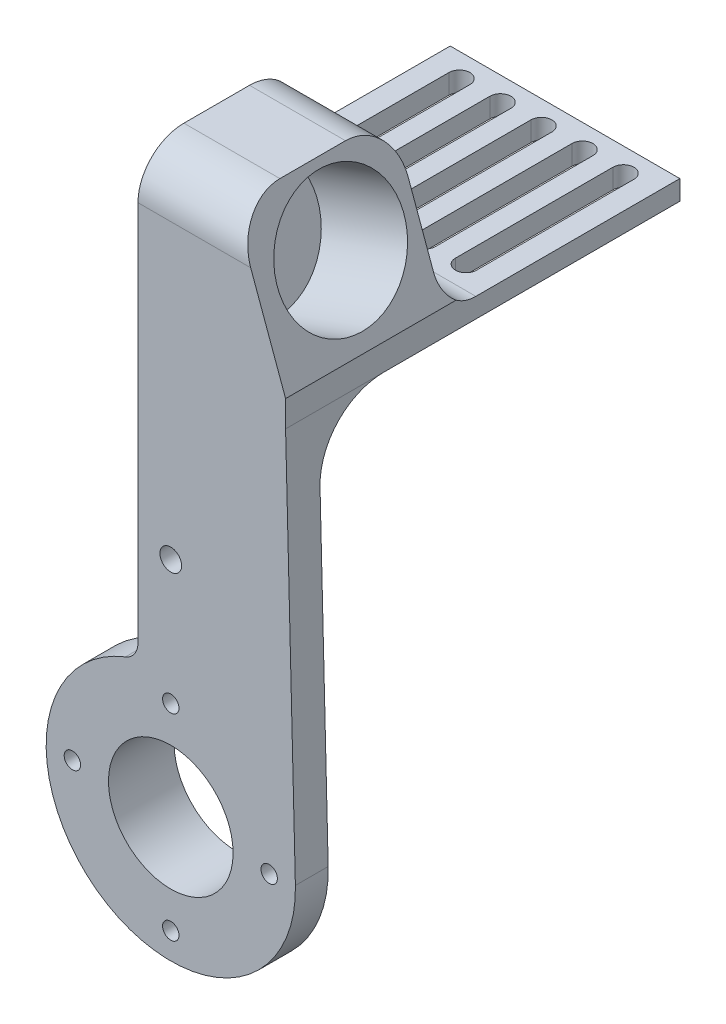
SolidWorks part; units mm, degrees
material "7075-T6 (SN)"
ref_plane "Front Plane" through (0, 0, 0) normal (0, 0, 1) x (1, 0, 0)
ref_plane "Top Plane" through (0, 0, 0) normal (0, 1, 0) x (1, 0, 0)
ref_plane "Right Plane" through (0, 0, 0) normal (1, 0, 0) x (0, 0, -1)
sketch "Sketch2" plane through (0, 0, 0) normal (0, 0, 1) x (1, 0, 0)
  line L0 (-18.994, 0.4767) -> (-17.5, 60)
  line L1 (-17.5, 60) -> (17.5, 60)
  line L2 (17.5, 60) -> (18.994, 0.4767)
  circle A0 centre (0, 0) radius 9.5
  arc A1 (-18.994, 0.4767) -> (18.994, 0.4767) centre (0, 0) ccw
  dimension "D1" = 19
  dimension "D2" = 38
  dimension "D3" = 60
  dimension "D4" = 35
extrude "Boss-Extrude1" add sketch "Sketch2" along normal blind 5
sketch "Sketch3" plane through (0, 60, 0) normal (0, 1, 0) x (1, 0, 0)
  line L1 (-17.5, -5) -> (17.5, -5)
  line L2 (-17.5, -5) -> (-17.5, 80.128)
  line L3 (-17.5, 80.128) -> (17.5, 80.128)
  line L4 (17.5, -5) -> (17.5, 80.128)
  dimension "D1" = 85.128
extrude "Boss-Extrude2" add sketch "Sketch3" along normal blind 3
sketch "Sketch4" plane through (0, 0, 0) normal (0, 0, -1) x (-1, 0, 0)
  circle A0 centre (0, 0) radius 13
  circle A2 centre (0, 0) radius 9.5
  circle A3 centre (0, 0) radius 9.5 construction
  dimension "D1" = 26
extrude "Boss-Extrude3" add sketch "Sketch4" along normal blind 5
sketch "Sketch5" plane through (0, 0, -80.128) normal (0, 0, -1) x (-1, 0, 0)
  line L0 (-17.5, 60) -> (-17.5, 51)
  line L1 (-17.5, 51) -> (17.5, 51)
  line L2 (17.5, 51) -> (17.5, 60)
  line L3 (17.5, 60) -> (-17.5, 60)
  dimension "D1" = 9
extrude "Boss-Extrude4" add sketch "Sketch5" against normal blind 3
hole_wizard "M3x0.5 Tapped Hole1" positions "Sketch8" profile "Sketch7" tap size "M3x0.5" standard "ANSI Metric"
sketch "Sketch8" plane through (0, 0, -80.128) normal (0, 0, 1) x (1, 0, 0)
  line L1 (-12, 55.5) -> (0, 55.5) construction
  line L2 (0, 55.5) -> (12, 55.5) construction
  line L5 (0, 55.5) -> (0, 63) construction
  line L6 (-17.5, 63) -> (17.5, 63) construction
  line L8 (17.5, 60) -> (-17.5, 60) construction
  point P2 (12, 55.5)
  point P4 (0, 55.5)
  point P6 (-12, 55.5)
  dimension "D1" = 12
  dimension "D2" = 4.5
sketch "Sketch7" plane through (12, 55.5, -80.128) normal (1, 0, 0) x (0, 1, 0)
  line L0 (0, 0) -> (0, 3)
  line L1 (0, 3) -> (1.25, 3)
  line L2 (1.25, 3) -> (1.25, 0)
  line L5 (1.25, 0) -> (0, 0)
  line L11 (0, -6.35) -> (0, 107.95) construction
  dimension "Thru Tap Drill Dia." = 2.5
  dimension "Thru Tap Drill Depth" = 3
cosmetic thread "Hole Thread5" parameters "D1"=3, "D2"=3
cosmetic thread "Hole Thread6" parameters "D1"=3, "D2"=3
cosmetic thread "Hole Thread7" parameters "D1"=3, "D2"=3
sketch "Sketch9" plane through (0, 63, 0) normal (0, 1, 0) x (1, 0, 0)
  line L0 (50, 7.5) -> (0, 7.5) construction
  line L2 (-17.5, -5) -> (17.5, -5) construction
  circle A0 centre (50, 7.5) radius 50 construction
  dimension "D1" = 100
  dimension "D2" = 50
  dimension "D3" = 12.5
ref_plane "Plane1" through (0, 0, -7.5) normal (0, 0, 1) x (1, 0, 0)
sketch "Sketch10" plane through (0, 0, 5) normal (0, 0, 1) x (1, 0, 0)
  line L0 (-5, 85.6129) -> (-5, 63)
  line L1 (-5, 85.6129) -> (9.6335, 85.6129)
  line L2 (9.6335, 85.6129) -> (17.5, 64)
  line L3 (17.5, 63) -> (-5, 63)
  line L4 (17.5, 64) -> (17.5, 63)
  line L6 (17.5, 63) -> (17.5, 60) construction
  line L7 (9.6335, 85.6129) -> (-0.7031, 81.8507) construction
  line L8 (-0.7031, 81.8507) -> (7.1634, 60.2378) construction
  line L9 (7.1634, 60.2378) -> (17.5, 64) construction
  line L10 (-17.5, 63) -> (17.5, 63) construction
  line L11 (17.5, 64) -> (5.4035, 64) construction
  dimension "D1" = 23
  dimension "D2" = 12.5
  dimension "D3" = 70
  dimension "D4" = 11
  dimension "D5" = 1
extrude "Boss-Extrude5" add sketch "Sketch10" against normal blind 24
sketch "Sketch11" plane through (-1.8214, 117.085, 0) normal (-0.9397, -0.342, 0) x (0, 0, -1)
  line L0 (7.5, 56.4919) -> (7.5, 33.4919) construction
  line L1 (-5, 56.4919) -> (-5, 60.2506) construction
  line L3 (19, 56.4919) -> (-5, 56.4919) construction
  line L4 (19, 33.4919) -> (-5, 33.4919) construction
  circle A0 centre (7.5, 44.4919) radius 9.652
  dimension "D1" = 19.304
  dimension "D2" = 12.5
  dimension "D3" = 11
extrude "Cut-Extrude1" cut sketch "Sketch11" along normal blind 14
sketch "Sketch12" plane through (0, 0, 5) normal (0, 0, 1) x (1, 0, 0)
  line L0 (-13.5489, 58) -> (13.5489, 58)
  line L1 (13.5489, 58) -> (14.7027, 12.0346)
  line L2 (17.5, 60) -> (-17.5, 60) construction
  line L3 (-14.7027, 12.0346) -> (-13.5489, 58)
  line L4 (-17.5, 60) -> (-18.994, 0.4767) construction
  line L5 (18.994, 0.4767) -> (17.5, 60) construction
  arc A0 (-18.994, 0.4767) -> (18.994, 0.4767) centre (0, 0) ccw construction
  arc A1 (14.7027, 12.0346) -> (-14.7027, 12.0346) centre (0, 0) ccw
  dimension "D1" = 2
  dimension "D2" = 4
extrude "Cut-Extrude2" cut sketch "Sketch12" against normal up to surface (5 mm away) up to face at (4.7485, 25.3692, 0)
sketch "Sketch14" plane through (0, 63, 0) normal (0, 1, 0) x (1, 0, 0)
  line L0 (-6.25, 39.5) -> (0, 39.5) construction
  line L1 (-14.1, 51.5) -> (-10.9, 51.5) construction
  line L2 (-14.1, 51.5) -> (-14.1, 27.5)
  line L3 (-14.1, 27.5) -> (-10.9, 27.5) construction
  line L4 (-10.9, 51.5) -> (-10.9, 27.5)
  line L5 (-35.75, 7.5) -> (35.75, 7.5) construction
  line L6 (-12.5, 51.5) -> (-12.5, 27.5) construction
  line L7 (-17.5, 80.128) -> (-17.5, -5) construction
  line L8 (-1.6, 51.5) -> (1.6, 51.5) construction
  line L9 (-1.6, 51.5) -> (-1.6, 27.5)
  line L10 (-1.6, 27.5) -> (1.6, 27.5) construction
  line L11 (1.6, 51.5) -> (1.6, 27.5)
  line L12 (0, 51.5) -> (0, 27.5) construction
  line L13 (10.9, 51.5) -> (14.1, 51.5) construction
  line L14 (10.9, 51.5) -> (10.9, 27.5)
  line L15 (10.9, 27.5) -> (14.1, 27.5) construction
  line L16 (14.1, 51.5) -> (14.1, 27.5)
  line L17 (12.5, 51.5) -> (12.5, 27.5) construction
  line L18 (0, 39.5) -> (6.25, 39.5) construction
  line L19 (-12.5, 39.5) -> (0, 39.5) construction
  line L20 (0, 39.5) -> (12.5, 39.5) construction
  line L21 (-12.5, 39.5) -> (-17.5, 39.5) construction
  line L22 (12.5, 39.5) -> (17.5, 39.5) construction
  line L23 (17.5, 19) -> (17.5, 80.128) construction
  line L24 (-7.85, 51.5) -> (-4.65, 51.5) construction
  line L25 (-7.85, 51.5) -> (-7.85, 27.5)
  line L26 (-7.85, 27.5) -> (-4.65, 27.5) construction
  line L27 (-4.65, 51.5) -> (-4.65, 27.5)
  line L28 (-6.25, 51.5) -> (-6.25, 27.5) construction
  line L29 (4.65, 51.5) -> (7.85, 51.5) construction
  line L30 (4.65, 51.5) -> (4.65, 27.5)
  line L31 (4.65, 27.5) -> (7.85, 27.5) construction
  line L32 (7.85, 51.5) -> (7.85, 27.5)
  line L33 (6.25, 51.5) -> (6.25, 27.5) construction
  line L34 (-12.5, 39.5) -> (-6.25, 39.5) construction
  arc A0 (-10.9, 51.5) -> (-14.1, 51.5) centre (-12.5, 51.5) ccw
  arc A1 (-14.1, 27.5) -> (-10.9, 27.5) centre (-12.5, 27.5) ccw
  arc A2 (1.6, 51.5) -> (-1.6, 51.5) centre (0, 51.5) ccw
  arc A3 (-1.6, 27.5) -> (1.6, 27.5) centre (0, 27.5) ccw
  arc A4 (14.1, 51.5) -> (10.9, 51.5) centre (12.5, 51.5) ccw
  arc A5 (10.9, 27.5) -> (14.1, 27.5) centre (12.5, 27.5) ccw
  arc A6 (-4.65, 51.5) -> (-7.85, 51.5) centre (-6.25, 51.5) ccw
  arc A7 (-7.85, 27.5) -> (-4.65, 27.5) centre (-6.25, 27.5) ccw
  arc A8 (7.85, 51.5) -> (4.65, 51.5) centre (6.25, 51.5) ccw
  arc A9 (4.65, 27.5) -> (7.85, 27.5) centre (6.25, 27.5) ccw
  dimension "D1" = 24
  dimension "D2" = 20
  dimension "D3" = 3.2
  dimension "D4" = 5
extrude "Cut-Extrude4" cut sketch "Sketch14" against normal up to surface (3 mm away) up to face at (4.375, 60, -38.564)
sketch "Sketch15" plane through (0, 63, 0) normal (0, 1, 0) x (1, 0, 0)
  line L0 (17.5, 19) -> (17.5, 80.128) construction
  line L1 (-17.5, 80.128) -> (17.5, 80.128)
  line L2 (-17.5, 80.128) -> (-17.5, 55.1)
  line L3 (-17.5, 55.1) -> (17.5, 55.1)
  line L4 (17.5, 80.128) -> (17.5, 55.1)
  arc A0 (1.6, 51.5) -> (-1.6, 51.5) centre (0, 51.5) ccw construction
  point P7 (0, 53.1)
  dimension "D1" = 2
extrude "Cut-Extrude5" cut sketch "Sketch15" against normal up to surface (12 mm away) up to face at (0, 51, -78.628)
sketch "Sketch18" plane through (0, 0, 5) normal (0, 0, 1) x (1, 0, 0)
  circle A0 centre (0, 0) radius 15 construction
  circle A1 centre (0, 15) radius 1.5
  circle A2 centre (0, -15) radius 1.5
  circle A3 centre (15, 0) radius 1.5
  circle A4 centre (-15, 0) radius 1.5
  dimension "D1" = 30
  dimension "D2" = 3
hole_wizard "M3x0.5 Tapped Hole2" positions "Sketch20" profile "Sketch19" tap size "M3x0.5" standard "BSI"
sketch "Sketch20" plane through (0, 0, 5) normal (0, 0, 1) x (1, 0, 0)
  point P0 (0, 15)
  point P3 (15, 0)
  point P6 (0, -15)
  point P9 (-15, 0)
sketch "Sketch19" plane through (0, 15, 5) normal (1, 0, 0) x (0, -1, 0)
  line L0 (0, 0) -> (0, 7.2511)
  line L1 (0, 7.2511) -> (1.25, 6.5)
  line L2 (1.25, 6.5) -> (1.25, 0)
  line L5 (1.25, 0) -> (0, 0)
  line L10 (0, 7.2511) -> (-1.25, 6.5) construction
  line L11 (0, -6.35) -> (0, 107.95) construction
  dimension "Tap Drill Dia." = 2.5
  dimension "Tap Drill Depth" = 6.5
  dimension "Drill Angle" = 118
cosmetic thread "Hole Thread8" parameters "D1"=3.5, "D2"=3
cosmetic thread "Hole Thread9" parameters "D1"=3.5, "D2"=3
cosmetic thread "Hole Thread10" parameters "D1"=3.5, "D2"=3
cosmetic thread "Hole Thread11" parameters "D1"=3.5, "D2"=3
fillet "Fillet7" radius 7 2 edges at (2.3168, 85.6129, 5) (2.3168, 85.6129, -19)
sketch "Sketch22" plane through (0, 0, 5) normal (0, 0, 1) x (1, 0, 0)
  line L0 (0, 0) -> (0, 34) construction
  line L1 (0, 0) -> (24.0416, 24.0416) construction
  line L2 (-5, 58) -> (-5, 18.3303)
  line L3 (13.5489, 58) -> (-13.5489, 58) construction
  line L4 (-5, 18.3303) -> (5, 18.3303)
  line L5 (5, 58) -> (5, 18.3303)
  line L6 (5, 58) -> (-5, 58)
  line L7 (0, 58) -> (0, 34) construction
  line L8 (24.0416, 29.0416) -> (18.277, 29.0416) construction
  line L9 (18.994, 0.4767) -> (17.5, 60) construction
  line L10 (18.277, 29.0416) -> (18.528, 19.0416) construction
  line L11 (18.528, 19.0416) -> (24.0416, 19.0416) construction
  circle A0 centre (0, 0) radius 37.5 construction
  circle A1 centre (0, 34) radius 2.25 construction
  circle A2 centre (0, 0) radius 34 construction
  circle A3 centre (24.0416, 24.0416) radius 2.25 construction
  arc A4 (14.7027, 12.0346) -> (-14.7027, 12.0346) centre (0, 0) ccw construction
  arc A5 (24.0416, 19.0416) -> (24.0416, 29.0416) centre (24.0416, 24.0416) ccw construction
  dimension "D1" = 68
  dimension "D2" = 75
  dimension "D3" = 4.5
  dimension "D6" = 10
  dimension "D4" = 45
  dimension "D5" = 5
extrude "Boss-Extrude6" add sketch "Sketch22" against normal up to surface (5 mm away) up to face at (1.25, 15, 0)
fillet "Fillet3" radius 5 1 edges
sketch "Sketch25" plane through (0, 0, 5) normal (0, 0, 1) x (1, 0, 0)
  line L0 (-5, 63) -> (-17.5, 63)
  line L1 (-5, 63) -> (17.5, 63) construction
  line L2 (-17.5, 63) -> (-18.994, 0.4767)
  line L4 (-5, 18.3303) -> (-5, 63)
  arc A0 (-5, 18.3303) -> (-18.994, 0.4767) centre (0, 0) ccw
extrude "Cut-Extrude6" cut sketch "Sketch25" against normal blind 25
fillet "Fillet5" radius 10 1 edges
fillet "Fillet4" radius 3 3 edges at (-5, 18.3303, 2.5) (-17.5, 61.5, -20) (-5, 61.5, -20)
hole_wizard "M4x0.7 Tapped Hole1" positions "Sketch24" profile "Sketch23" tap size "M4x0.7" standard "BSI" end condition through all
sketch "Sketch24" plane through (0, 0, 5) normal (0, 0, 1) x (1, 0, 0)
  point P0 (0, 34)
sketch "Sketch23" plane through (0, 34, 5) normal (1, 0, 0) x (0, -1, 0)
  line L0 (0, 0) -> (0, 60.1)
  line L1 (0, 60.1) -> (1.65, 60.1)
  line L2 (1.65, 60.1) -> (1.65, 0)
  line L5 (1.65, 0) -> (0, 0)
  line L11 (0, -6.35) -> (0, 107.95) construction
  dimension "Thru Tap Drill Dia." = 3.3
  dimension "Thru Tap Drill Depth" = 60.1
cosmetic thread "Hole Thread13" parameters "D2"=4
